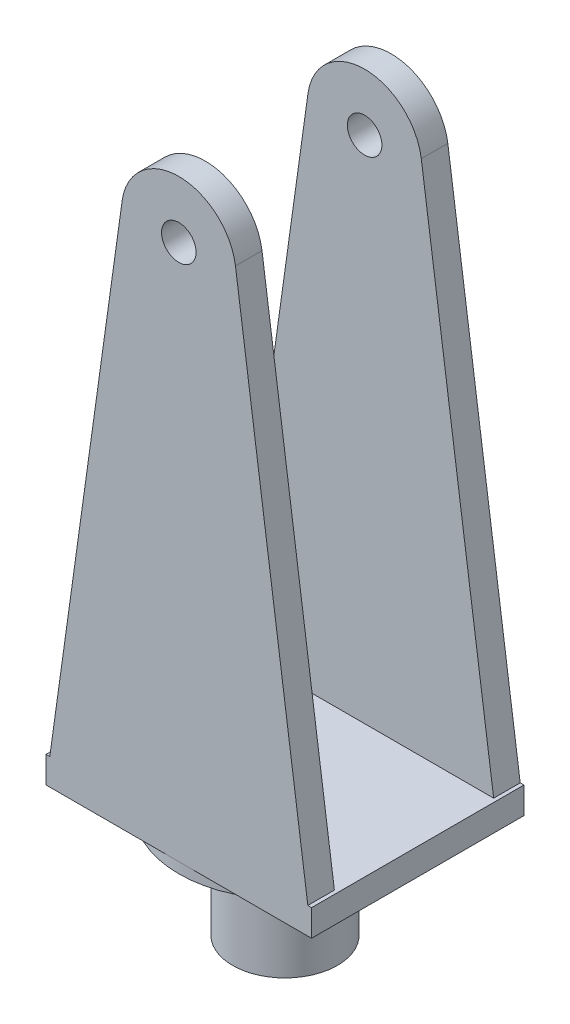
SolidWorks part; units mm, degrees
material "PBT General Purpose"
ref_plane "Front Plane" through (0, 0, 0) normal (0, 0, 1) x (1, 0, 0)
ref_plane "Top Plane" through (0, 0, 0) normal (0, 1, 0) x (1, 0, 0)
ref_plane "Right Plane" through (0, 0, 0) normal (1, 0, 0) x (0, 0, -1)
sketch "Sketch1" plane through (0, 0, 0) normal (0, 1, 0) x (1, 0, 0)
  line L1 (-12.5, -10) -> (12.5, -10)
  line L2 (-12.5, -10) -> (-12.5, 10)
  line L3 (-12.5, 10) -> (12.5, 10)
  line L4 (12.5, -10) -> (12.5, 10)
  line L5 (-12.5, -10) -> (12.5, 10) construction
  line L6 (-12.5, 10) -> (12.5, -10) construction
  point P0 (0, 0)
  dimension "D1" = 20
  dimension "D2" = 25
extrude "Boss-Extrude1" add sketch "Sketch1" along normal blind 2.5
ref_plane "Plane1" through (0, 0, 0) normal (0, 0, -1) x (-1, 0, 0)
sketch "Sketch4" plane through (0, 0, 0) normal (0, -1, 0) x (1, 0, 0)
  line L0 (12.5, -10) -> (-12.5, -10) construction
  circle A0 centre (0, 0) radius 10
extrude "Boss-Extrude3" add sketch "Sketch4" along normal blind 1
sketch "Sketch5" plane through (0, -1, 0) normal (0, -1, 0) x (1, 0, 0)
  circle A0 centre (0, 0) radius 4.9365
  dimension "D1" = 9.873
extrude "Boss-Extrude4" add sketch "Sketch5" along normal blind 10
sketch "Sketch6" plane through (0, 0, -10) normal (0, 0, -1) x (-1, 0, 0)
  line L1 (12.5, 0) -> (-12.5, 0)
  line L2 (12.5, 0) -> (5.3349, 51.2454)
  line L5 (-10, -1) -> (10, -1) construction
  line L6 (-10, -1) -> (10, -1)
  line L7 (0, -1) -> (0, 50.5) construction
  line L8 (-12.5, 0) -> (-5.3349, 51.2454)
  line L9 (0, 52.127) -> (0, 55.8867) construction
  circle A0 centre (0, 50.5) radius 1.627
  arc A1 (5.3349, 51.2454) -> (-5.3349, 51.2454) centre (0, 50.5) ccw
  line M10 (12.5, 2.5) -> (-12.5, 2.5)
  dimension "D2" = 3.254
  dimension "D1" = 51.5
  dimension "D3" = 3.7597
extrude "Boss-Extrude5" add sketch "Sketch6" against normal blind 2.5 contours L2 A1 L8 A0 M10 region at (0, 24.7101, -10)
mirror "Mirror2" about plane through (0, 0, 0) normal (0, 0, -1) of "Boss-Extrude5"
